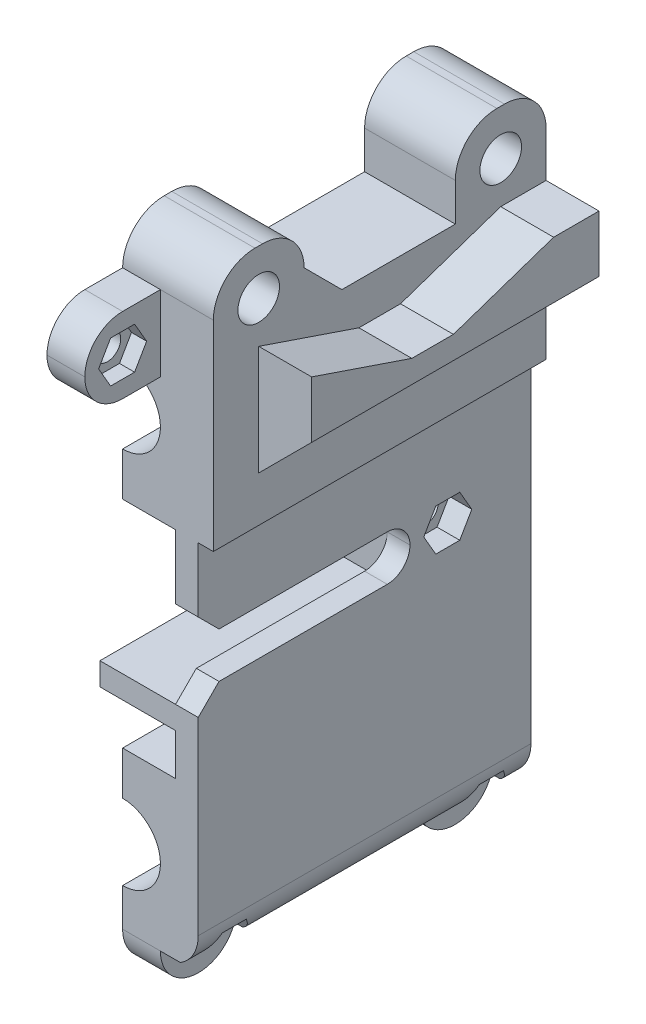
SolidWorks part; units mm, degrees
ref_plane "Front Plane" through (0, 0, 0) normal (0, 0, 1) x (1, 0, 0)
ref_plane "Top Plane" through (0, 0, 0) normal (0, 1, 0) x (1, 0, 0)
ref_plane "Right Plane" through (0, 0, 0) normal (1, 0, 0) x (0, 0, -1)
sketch "Sketch1" plane through (0, 0, 0) normal (1, 0, 0) x (0, 0, -1)
  line L1 (-22, -16) -> (22, -16)
  line L2 (-22, -16) -> (-22, 16)
  line L3 (-22, 16) -> (22, 16)
  line L4 (22, -16) -> (22, 16)
  line L5 (-22, -16) -> (22, 16) construction
  line L6 (-22, 16) -> (22, -16) construction
  point P0 (0, 0)
  dimension "D1" = 44
  dimension "D2" = 32
extrude "Boss-Extrude1" add sketch "Sketch1" along normal blind 12
sketch "Sketch2" plane through (0, 0, 0) normal (1, 0, 0) x (0, 0, -1)
  line L0 (-22, -16) -> (22, -16) construction
  line L1 (12.25, -13) -> (-12.25, -13)
  line L2 (12.25, -13) -> (12.25, 2.5)
  line L3 (12.25, 2.5) -> (-12.25, 2.5)
  line L4 (-12.25, -13) -> (-12.25, 2.5)
  line L5 (12.25, -13) -> (-12.25, 2.5) construction
  line L6 (12.25, 2.5) -> (-12.25, -13) construction
  point P0 (0, -5.25)
  dimension "D1" = 24.5
  dimension "D2" = 15.5
  dimension "D3" = 0
  dimension "D4" = 3
extrude "Cut-Extrude1" cut sketch "Sketch2" along normal blind 7.75 contours L2 L1 L4 L3
fillet "Fillet1" radius 7.75 2 edges at (7.75, 2.5, 0) (7.75, -13, 0)
sketch "Sketch3" plane through (0, 0, -12.25) normal (0, 0, 1) x (1, 0, 0)
  arc A0 (0, -13) -> (7.75, -5.25) centre (0, -5.25) ccw construction
  arc A1 (0, -13) -> (7.75, -5.25) centre (0, -5.25) ccw
  circle A2 centre (0, -5.25) radius 5
  line M3 (0, 2.5) -> (0, -13)
  dimension "D1" = 10
extrude "Cut-Extrude2" cut sketch "Sketch3" against normal through all both and the other way through all contours A2 M3 | A2 M3 region at (2.1221, -5.25, -12.25) region at (-2.1221, -5.25, -12.25)
sketch "Sketch4" plane through (12, 0, 0) normal (1, 0, 0) x (0, 0, -1)
  line L0 (22, 16) -> (-22, 16) construction
  line L2 (-10, 16) -> (10, 16)
  line L3 (-10, 16) -> (-10, 5.5)
  line L4 (-10, 5.5) -> (10, 5.5)
  line L5 (10, 16) -> (10, 5.5)
  circle A0 centre (-16, 10) radius 2.75
  circle A1 centre (16, 10) radius 2.75
  dimension "D1" = 5.5
  dimension "D2" = 5.5
  dimension "D3" = 6
  dimension "D4" = 6
  dimension "D5" = 6
  dimension "D6" = 6
  dimension "D7" = 32
  dimension "D8" = 10
  dimension "D9" = 10.5
extrude "Cut-Extrude3" cut sketch "Sketch4" against normal through all
sketch "Sketch5" plane through (12, 0, 0) normal (1, 0, 0) x (0, 0, -1)
  line L0 (-16, 10) -> (-16, 4.5)
  line L1 (-2.75, -3) -> (2.75, -3)
  line L2 (-2.75, -3) -> (-2.75, 0)
  line L3 (-2.75, 0) -> (2.75, 0)
  line L4 (2.75, -3) -> (2.75, 0)
  line L5 (-2.75, -3) -> (2.75, 0) construction
  line L6 (-2.75, 0) -> (2.75, -3) construction
  line L7 (16, 10) -> (16, 4.5)
  line L8 (-2.75, 0) -> (-16, 4.5)
  line L9 (2.75, 0) -> (16, 4.5)
  line L10 (2.75, -3) -> (16, 4.5)
  line L11 (-2.75, -3) -> (-16, 4.5)
  line L12 (16, 4.5) -> (16, -3)
  line L13 (16, -3) -> (2.75, -3)
  line L14 (-2.75, -3) -> (-16, -3)
  line L15 (-16, -3) -> (-16, 4.5)
  circle A0 centre (16, 10) radius 2.75 construction
  circle A1 centre (16, 10) radius 2.75
  circle A2 centre (-16, 10) radius 2.75 construction
  circle A3 centre (-16, 10) radius 2.75
  point P0 (0, -1.5)
  dimension "D1" = 10
  dimension "D2" = 3
  dimension "D3" = 5.5
  dimension "D4" = 0
  dimension "D5" = 5.5
  dimension "D6" = 5.5
extrude "Boss-Extrude4" add sketch "Sketch5" along normal blind 7 contours L15 L14 L11 | L11 L2 L8 | L1 L4 L3 L2 | L4 L10 L9 | L13 L12 L10 region at (12, 0.5, 7.1667) region at (12, -0.5, 11.5833) region at (12, -1.5, 0) region at (12, 0.5, -7.1667) region at (12, -0.5, -11.5833)
chamfer "Chamfer1" distance 7 angle 45 1 edges at (12, -3, 0)
sketch "Sketch6" plane through (12, 0, 0) normal (1, 0, 0) x (0, 0, -1)
  line L0 (16, -3) -> (-16, -3) construction
  line L1 (16, -3) -> (-16, -3)
  line L2 (16, -10) -> (-16, -10) construction
  line L3 (-13, -3) -> (13, -3)
  line L4 (-13, -3) -> (-13, -10)
  line L5 (-13, -10) -> (13, -10)
  line L6 (13, -3) -> (13, -10)
  line L7 (-16, -10) -> (-16, -3) construction
  line L8 (10, 5.5) -> (-10, 5.5)
  line L9 (-10, 5.5) -> (-10, 16)
  line L10 (-10, 16) -> (-22, 16)
  line L11 (-22, 16) -> (-22, -16)
  line L12 (-22, -16) -> (22, -16)
  line L13 (22, -16) -> (22, 16)
  line L14 (22, 16) -> (10, 16)
  line L15 (10, 16) -> (10, 5.5)
  line L16 (10, 5.5) -> (-10, 5.5)
  line L17 (-10, 5.5) -> (-10, 16)
  line L18 (-10, 16) -> (-22, 16)
  line L19 (-22, 16) -> (-22, -16)
  line L20 (-22, -16) -> (22, -16)
  line L21 (22, -16) -> (22, 16)
  line L22 (22, 16) -> (10, 16)
  line L23 (10, 16) -> (10, 5.5)
  line L24 (16, 4.5) -> (16, -10) construction
  line L25 (-2.75, 0) -> (2.75, 0) construction
  line L26 (-1.5, -3) -> (1.5, -3)
  line L27 (-1.5, -3) -> (-1.5, -10)
  line L28 (-1.5, -10) -> (1.5, -10)
  line L29 (1.5, -3) -> (1.5, -10)
  point P26 (0, 0)
  line M13 (16, -10) -> (-16, -10)
  dimension "D2" = 3
  dimension "D3" = 3
  dimension "D4" = 3
  dimension "D5" = 1.5
  dimension "D1" = 0
extrude "Cut-Extrude5" cut sketch "Sketch6" along normal through all contours L27 L1 L4 L5 | L1 L29 L6 M13 region at (12, -6.5, -7.25) region at (12, -6.5, 7.25)
fillet "Fillet4" radius 5.5 2 edges at (6, 16, -22) (6, 16, 22)
sketch "Sketch7" plane through (0, 0, 0) normal (1, 0, 0) x (0, 0, -1)
  line L0 (-22, -16) -> (22, -16) construction
  line L1 (5, -16) -> (-5, -16)
  line L2 (5, -16) -> (5, -26)
  line L3 (5, -26) -> (-5, -26)
  line L4 (-5, -16) -> (-5, -26)
  circle A0 centre (0, -21) radius 2
  dimension "D4" = 4
  dimension "D1" = 10
  dimension "D2" = 10
  dimension "D3" = 5
  dimension "D5" = 5
extrude "Boss-Extrude5" [suppressed] add sketch "Sketch7" along normal blind 5
sketch "Sketch8" [suppressed] plane through (5, 0, 0) normal (1, 0, 0) x (0, 0, -1)
  line L1 (0, -24.1754) -> (2.75, -22.5877)
  line L2 (2.75, -22.5877) -> (2.75, -19.4123)
  line L3 (2.75, -19.4123) -> (0, -17.8246)
  line L4 (0, -17.8246) -> (-2.75, -19.4123)
  line L5 (-2.75, -19.4123) -> (-2.75, -22.5877)
  line L6 (-2.75, -22.5877) -> (0, -24.1754)
  circle A0 centre (0, -21) radius 2 construction
  circle A1 centre (0, -21) radius 2
  circle A2 centre (0, -21) radius 2.75 construction
  dimension "D1" = 5.5
extrude "Cut-Extrude6" [suppressed] cut sketch "Sketch8" against normal blind 2
fillet "Fillet5" [suppressed] radius 5
sketch "Sketch9" plane through (0, 0, 0) normal (-1, 0, 0) x (0, 0, 1)
  line L1 (-16, 5.3812) -> (-12, 7.6906)
  line L2 (-12, 7.6906) -> (-12, 12.3094)
  line L3 (-12, 12.3094) -> (-16, 14.6188)
  line L4 (-16, 14.6188) -> (-20, 12.3094)
  line L5 (-20, 12.3094) -> (-20, 7.6906)
  line L6 (-20, 7.6906) -> (-16, 5.3812)
  line L7 (16, 5.3812) -> (20, 7.6906)
  line L8 (20, 7.6906) -> (20, 12.3094)
  line L9 (20, 12.3094) -> (16, 14.6188)
  line L10 (16, 14.6188) -> (12, 12.3094)
  line L11 (12, 12.3094) -> (12, 7.6906)
  line L12 (12, 7.6906) -> (16, 5.3812)
  circle A0 centre (16, 10) radius 2.75 construction
  circle A1 centre (-16, 10) radius 2.75 construction
  circle A2 centre (16, 10) radius 2.75
  circle A3 centre (-16, 10) radius 2.75
  circle A4 centre (-16, 10) radius 4 construction
  circle A5 centre (16, 10) radius 4 construction
  point P6 (20, 10)
  dimension "D1" = 8
  dimension "D2" = 8
extrude "Cut-Extrude7" [suppressed] cut sketch "Sketch9" against normal blind 4
ref_plane "Plane1" through (0, -30.25, 0) normal (0, -1, 0) x (-1, 0, 0)
sketch "Sketch10" plane through (0, -16, 0) normal (0, -1, 0) x (1, 0, 0)
  line L0 (12, 22) -> (0, 22) construction
  line L1 (7, 22) -> (10, 22)
  line L2 (7, 22) -> (7, -22)
  line L3 (7, -22) -> (10, -22)
  line L4 (10, 22) -> (10, -22)
  line L5 (12, -22) -> (0, -22) construction
  line L6 (0, 22) -> (0, -22) construction
  dimension "D1" = 3
  dimension "D2" = 7
extrude "Boss-Extrude6" add sketch "Sketch10" along normal blind 28.5
sketch "Sketch11" plane through (0, -44.5, 0) normal (0, -1, 0) x (1, 0, 0)
  line L1 (10, -22) -> (0, -22)
  line L2 (10, -22) -> (10, 22)
  line L3 (10, 22) -> (0, 22)
  line L4 (0, -22) -> (0, 22)
  dimension "D1" = 44
  dimension "D2" = 10
extrude "Boss-Extrude7" add sketch "Sketch11" along normal blind 21.5
sketch "Sketch12" plane through (0, 0, 0) normal (-1, 0, 0) x (0, 0, 1)
  line L0 (22, -44.5) -> (-22, -44.5) construction
  line L1 (-12.25, -63) -> (12.25, -63)
  line L2 (-12.25, -63) -> (-12.25, -47.5)
  line L3 (-12.25, -47.5) -> (12.25, -47.5)
  line L4 (12.25, -63) -> (12.25, -47.5)
  dimension "D1" = 24.5
  dimension "D2" = 15.5
  dimension "D3" = 3
  dimension "D4" = 12.25
extrude "Cut-Extrude8" cut sketch "Sketch12" against normal blind 7.75
fillet "Fillet6" radius 7.75 2 edges at (7.75, -63, 0) (7.75, -47.5, 0)
sketch "Sketch13" plane through (0, 0, 22) normal (0, 0, 1) x (1, 0, 0)
  arc A0 (7.75, -55.25) -> (0, -47.5) centre (0, -55.25) ccw construction
  arc A1 (7.75, -55.25) -> (0, -47.5) centre (0, -55.25) ccw
  circle A2 centre (0, -55.25) radius 5
  line M9 (0, -44.5) -> (0, -66)
  dimension "D1" = 10
extrude "Cut-Extrude9" cut sketch "Sketch13" against normal through all contours A2 M9 region at (2.1221, -55.25, 22)
sketch "Sketch14" plane through (7, 0, 0) normal (-1, 0, 0) x (0, 0, 1)
  line L1 (-22, -16) -> (-6, -16)
  line L2 (-22, -16) -> (-22, -36)
  line L3 (-22, -36) -> (-6, -36)
  line L4 (-6, -16) -> (-6, -36)
  dimension "D1" = 20
  dimension "D2" = 16
extrude "Boss-Extrude8" add sketch "Sketch14" along normal blind 13.5
sketch "Sketch15" plane through (-6.5, 0, 0) normal (-1, 0, 0) x (0, 0, 1)
  line L0 (-6.6, -30.25) -> (6.6, -30.25) construction
  line L1 (-22, -16) -> (-22, -36) construction
  line L2 (-22, -29) -> (-11, -29)
  line L3 (-22, -29) -> (-22, -31.5)
  line L4 (-22, -31.5) -> (-11, -31.5)
  line L5 (-11, -29) -> (-11, -31.5)
  circle A0 centre (-11, -30.25) radius 3
  line M6 (-22, -16) -> (-22, -36)
  dimension "D2" = 6
  dimension "D1" = 0
  dimension "D3" = 2.5
  dimension "D4" = 1.25
  dimension "D5" = 11
extrude "Cut-Extrude10" cut sketch "Sketch15" against normal blind 10 contours A0 L2 L4 M6 | L2 A0 L4 L5 | L4 A0 L2 L5 region at (-6.5, -30.25, -17.955) region at (-6.5, -30.25, -10.4952) region at (-6.5, -30.25, -12.4565)
fillet "Fillet7" radius 2 2 edges at (-1.5, -29, -13.7272) (-1.5, -31.5, -13.7272)
sketch "Sketch16" plane through (3.5, 0, 0) normal (-1, 0, 0) x (0, 0, 1)
  arc A0 (-13.2798, -32.2) -> (-13.2798, -28.3) centre (-11, -30.25) ccw construction
  arc A1 (-13.2798, -32.2) -> (-13.2798, -28.3) centre (-11, -30.25) ccw
  circle A2 centre (-11, -30.25) radius 1.75
  point P4 (0, 0)
  dimension "D1" = 3.5
extrude "Cut-Extrude11" cut sketch "Sketch16" against normal through all contours A2 region at (3.5, -30.25, -11)
sketch "Sketch17" plane through (10, 0, 0) normal (1, 0, 0) x (0, 0, -1)
  line L1 (14.1754, -30.25) -> (12.5877, -27.5)
  line L2 (12.5877, -27.5) -> (9.4123, -27.5)
  line L3 (9.4123, -27.5) -> (7.8246, -30.25)
  line L4 (7.8246, -30.25) -> (9.4123, -33)
  line L5 (9.4123, -33) -> (12.5877, -33)
  line L6 (12.5877, -33) -> (14.1754, -30.25)
  circle A0 centre (11, -30.25) radius 1.75 construction
  circle A1 centre (11, -30.25) radius 1.75
  circle A2 centre (11, -30.25) radius 2.75 construction
  dimension "D1" = 5.5
extrude "Cut-Extrude12" cut sketch "Sketch17" against normal blind 3
sketch "Sketch18" plane through (7, 0, 0) normal (-1, 0, 0) x (0, 0, 1)
  line L0 (22, -44.5) -> (22, -16) construction
  line L1 (-22, -36) -> (22, -36)
  line L2 (-22, -36) -> (-22, -39)
  line L3 (-22, -39) -> (22, -39)
  line L4 (22, -36) -> (22, -39)
  dimension "D1" = 3
extrude "Boss-Extrude9" add sketch "Sketch18" along normal blind 10
sketch "Sketch20" plane through (-6.5, 0, 0) normal (-1, 0, 0) x (0, 0, 1)
  line L1 (-22, -16) -> (-11, -16)
  line L2 (-22, -16) -> (-22, -25)
  line L3 (-22, -25) -> (-11, -25)
  line L4 (-11, -16) -> (-11, -25)
  dimension "D1" = 9
  dimension "D2" = 11
extrude "Cut-Extrude13" cut sketch "Sketch20" against normal up to surface (13.5 mm away) up to face at (7, -26, 8)
sketch "Sketch21" plane through (0, 0, -11) normal (0, 0, -1) x (-1, 0, 0)
  line L0 (0, -16) -> (6.5, -16) construction
  circle A0 centre (0, -20.5) radius 1.75
  dimension "D2" = 3.5
  dimension "D1" = 4.5
extrude "Cut-Extrude14" cut sketch "Sketch21" against normal up to surface (5 mm away) up to face at (-0.3333, -26, -6)
sketch "Sketch22" plane through (0, 0, -11) normal (0, 0, -1) x (-1, 0, 0)
  line L1 (3.1754, -20.5) -> (1.5877, -17.75)
  line L2 (1.5877, -17.75) -> (-1.5877, -17.75)
  line L3 (-1.5877, -17.75) -> (-3.1754, -20.5)
  line L4 (-3.1754, -20.5) -> (-1.5877, -23.25)
  line L5 (-1.5877, -23.25) -> (1.5877, -23.25)
  line L6 (1.5877, -23.25) -> (3.1754, -20.5)
  circle A0 centre (0, -20.5) radius 1.75 construction
  circle A1 centre (0, -20.5) radius 1.75
  circle A2 centre (0, -20.5) radius 2.75 construction
  dimension "D1" = 5.5
extrude "Cut-Extrude15" cut sketch "Sketch22" against normal blind 2
sketch "Sketch23" plane through (7, 0, 0) normal (-1, 0, 0) x (0, 0, 1)
  line L0 (-6.6, -30.25) -> (6.6, -30.25) construction
  line L1 (-6, -27.25) -> (22, -27.25)
  line L2 (-6, -27.25) -> (-6, -33.25)
  line L3 (-6, -33.25) -> (22, -33.25)
  line L4 (22, -27.25) -> (22, -33.25)
  line L5 (-6, -27.25) -> (22, -33.25) construction
  line L6 (-6, -33.25) -> (22, -27.25) construction
  line L7 (-6, -36) -> (-6, -16) construction
  line L8 (22, -36) -> (22, -16) construction
  point P0 (8, -30.25)
  dimension "D1" = 0
  dimension "D2" = 0
  dimension "D3" = 0
  dimension "D4" = 6
extrude "Cut-Extrude16" cut sketch "Sketch23" against normal through all
fillet "Fillet8" radius 3 2 edges at (8.5, -27.25, -6) (8.5, -33.25, -6)
chamfer "Chamfer2" distance 2.75 angle 45 2 edges at (8.5, -27.25, 22) (8.5, -33.25, 22)
chamfer "Chamfer3" distance 3 angle 45 1 edges at (0.25, -25, -11)
fillet "Fillet9" radius 3 1 edges at (-6.5, -16, -8.5)
ref_plane "Plane2" through (0, 5.5, -10) normal (0, 1, 0) x (1, 0, 0)
sketch "Sketch25" plane through (0, 0, 0) normal (-1, 0, 0) x (0, 0, 1)
  line L1 (22, 10.5) -> (32, 10.5)
  line L2 (22, 10.5) -> (22, 0.5)
  line L3 (22, 0.5) -> (32, 0.5)
  line L4 (32, 10.5) -> (32, 0.5)
  dimension "D1" = 10
  dimension "D2" = 10
extrude "Boss-Extrude12" add sketch "Sketch25" against normal blind 5
fillet "Fillet11" radius 5 2 edges at (2.5, 0.5, 32) (2.5, 10.5, 32)
sketch "Sketch26" plane through (0, 0, 0) normal (-1, 0, 0) x (0, 0, 1)
  line L0 (-12.25, -63) -> (12.25, -63) construction
  line L1 (-22, -60.25) -> (-12, -60.25)
  line L2 (-22, -60.25) -> (-22, -70.25)
  line L3 (-22, -70.25) -> (-12, -70.25)
  line L4 (-12, -60.25) -> (-12, -70.25)
  line L5 (22, -60.25) -> (12, -60.25)
  line L6 (22, -60.25) -> (22, -70.25)
  line L7 (22, -70.25) -> (12, -70.25)
  line L8 (12, -60.25) -> (12, -70.25)
  line L9 (12.2369, -63) -> (12, -63)
  line L10 (12.2369, -63) -> (12.2369, -60.25)
  line L11 (12.2369, -60.25) -> (12, -60.25)
  line L12 (12, -63) -> (12, -60.25)
  line L14 (-12.25, -63) -> (-12, -63)
  line L15 (-12.25, -63) -> (-12.25, -60.25)
  line L16 (-12.25, -60.25) -> (-12, -60.25)
  line L17 (-12, -63) -> (-12, -60.25)
  line M14 (-22, -66) -> (22, -66)
  dimension "D1" = 10
  dimension "D2" = 10
  dimension "D3" = 10
  dimension "D4" = 10
extrude "Boss-Extrude13" add sketch "Sketch26" against normal blind 5 contours L4 L2 L3 M14 | L8 L7 L6 M14 region at (0, -68.125, 17) region at (0, -68.125, -17)
sketch "Sketch27" plane through (0, 0, 0) normal (-1, 0, 0) x (0, 0, 1)
  line L0 (-22, -70.25) -> (-12, -70.25) construction
  line L1 (-22, -70.25) -> (-22, -60.25) construction
  line L2 (22, -70.25) -> (22, -60.25) construction
  line L3 (22, -70.25) -> (12, -70.25) construction
  circle A0 centre (-17, -65.25) radius 1.75
  circle A1 centre (17, -65.25) radius 1.75
  point P8 (-22, -65.25)
  dimension "D5" = 3.5
  dimension "D6" = 3.5
  dimension "D1" = 5
  dimension "D2" = 5
  dimension "D3" = 5
  dimension "D4" = 5
extrude "Cut-Extrude17" cut sketch "Sketch27" against normal through all both and the other way through all
sketch "Sketch28" plane through (5, 0, 0) normal (1, 0, 0) x (0, 0, -1)
  line L1 (-13.8246, -65.25) -> (-15.4123, -62.5)
  line L2 (-15.4123, -62.5) -> (-18.5877, -62.5)
  line L3 (-18.5877, -62.5) -> (-20.1754, -65.25)
  line L4 (-20.1754, -65.25) -> (-18.5877, -68)
  line L5 (-18.5877, -68) -> (-15.4123, -68)
  line L6 (-15.4123, -68) -> (-13.8246, -65.25)
  line L7 (20.1754, -65.25) -> (18.5877, -62.5)
  line L8 (18.5877, -62.5) -> (15.4123, -62.5)
  line L9 (15.4123, -62.5) -> (13.8246, -65.25)
  line L10 (13.8246, -65.25) -> (15.4123, -68)
  line L11 (15.4123, -68) -> (18.5877, -68)
  line L12 (18.5877, -68) -> (20.1754, -65.25)
  circle A0 centre (17, -65.25) radius 1.75 construction
  circle A1 centre (-17, -65.25) radius 1.75 construction
  circle A2 centre (17, -65.25) radius 1.75
  circle A3 centre (-17, -65.25) radius 1.75
  circle A4 centre (-17, -65.25) radius 2.75 construction
  circle A5 centre (17, -65.25) radius 2.75 construction
  dimension "D1" = 5.5
  dimension "D2" = 5.5
extrude "Cut-Extrude19" cut sketch "Sketch28" against normal blind 2 and the other way through all
fillet "Fillet14" radius 5 1 edges at (10, -66, 20.8712)
fillet "Fillet15" radius 5 4 edges at (2.5, -70.25, 12) (2.5, -70.25, -12) (2.5, -70.25, -22) (2.5, -70.25, 22)
sketch "Sketch29" plane through (0, 0, 0) normal (-1, 0, 0) x (0, 0, 1)
  arc A0 (32, 5.5) -> (27, 10.5) centre (27, 5.5) ccw construction
  arc A1 (32, 5.5) -> (27, 10.5) centre (27, 5.5) ccw
  circle A2 centre (27, 5.5) radius 1.75
  dimension "D1" = 3.5
extrude "Cut-Extrude20" cut sketch "Sketch29" against normal through all both and the other way through all contours A2 region at (0, 5.5, 27)
sketch "Sketch30" plane through (5, 0, 0) normal (1, 0, 0) x (0, 0, -1)
  line L1 (-23.8246, 5.5) -> (-25.4123, 8.25)
  line L2 (-25.4123, 8.25) -> (-28.5877, 8.25)
  line L3 (-28.5877, 8.25) -> (-30.1754, 5.5)
  line L4 (-30.1754, 5.5) -> (-28.5877, 2.75)
  line L5 (-28.5877, 2.75) -> (-25.4123, 2.75)
  line L6 (-25.4123, 2.75) -> (-23.8246, 5.5)
  circle A0 centre (-27, 5.5) radius 1.75 construction
  circle A1 centre (-27, 5.5) radius 1.75
  circle A2 centre (-27, 5.5) radius 2.75 construction
  dimension "D1" = 5.5
extrude "Cut-Extrude21" cut sketch "Sketch30" against normal blind 2
fillet "Fillet17" radius 5.5 2 edges at (6, 16, -10) (6, 16, 10)
chamfer "Chamfer4" distance 5 angle 45 1 edges at (6, 5.5, 10)
sketch "Sketch32" plane through (0, 0, -16) normal (0, 0, -1) x (-1, 0, 0)
  line L4 (-12, -10) -> (-12, 4.5)
  line L5 (-12, 4.5) -> (-19, 4.5)
  line L6 (-19, 4.5) -> (-19, -3)
  line L7 (-19, -3) -> (-12, -10)
  line L8 (-12, -10) -> (-12, 4.5)
  line L9 (-12, 4.5) -> (-19, 4.5)
  line L10 (-19, 4.5) -> (-19, -3)
  line L11 (-19, -3) -> (-12, -10)
  dimension "D1" = 0
extrude "Boss-Extrude14" add sketch "Sketch32" along normal up to surface (6 mm away) up to face at (2.6074, -30.6323, -22)
sketch "Sketch33" plane through (0, 0, 0) normal (-1, 0, 0) x (0, 0, 1)
  line L1 (11.3812, 10) -> (13.6906, 6)
  line L2 (13.6906, 6) -> (18.3094, 6)
  line L3 (18.3094, 6) -> (20.6188, 10)
  line L4 (20.6188, 10) -> (18.3094, 14)
  line L5 (18.3094, 14) -> (13.6906, 14)
  line L6 (13.6906, 14) -> (11.3812, 10)
  line L7 (-11.3812, 10) -> (-13.6906, 14)
  line L8 (-13.6906, 14) -> (-18.3094, 14)
  line L9 (-18.3094, 14) -> (-20.6188, 10)
  line L10 (-20.6188, 10) -> (-18.3094, 6)
  line L11 (-18.3094, 6) -> (-13.6906, 6)
  line L12 (-13.6906, 6) -> (-11.3812, 10)
  circle A0 centre (-16, 10) radius 2.75 construction
  circle A1 centre (-16, 10) radius 2.75
  circle A2 centre (16, 10) radius 2.75 construction
  circle A3 centre (16, 10) radius 2.75
  circle A4 centre (16, 10) radius 4 construction
  circle A5 centre (-16, 10) radius 4 construction
  dimension "D1" = 8
  dimension "D2" = 8
extrude "Cut-Extrude22" cut sketch "Sketch33" against normal blind 4.5
chamfer "Chamfer11" distance 7 angle 45 2 edges at (15.5, -3, 13) (15.5, -3, -1.5)
sketch "Sketch34" plane through (5, 0, 0) normal (1, 0, 0) x (0, 0, -1)
  line L0 (13.8246, -65.25) -> (15.4123, -68) construction
  line L1 (-19.7424, -66) -> (-20.1754, -65.25) construction
  line L2 (13.8246, -65.25) -> (15.4123, -68)
  line L3 (-19.7424, -66) -> (-20.1754, -65.25)
  line L5 (-24.8945, -70.6786) -> (23.1824, -70.6786)
  line L6 (-24.8945, -70.6786) -> (-24.8945, -65.25)
  line L7 (-24.8945, -65.25) -> (23.1824, -65.25)
  line L8 (23.1824, -70.6786) -> (23.1824, -65.25)
extrude "Cut-Extrude24" cut sketch "Sketch34" along normal through all contours L8 L0 L1 L2 L3 L5 L6 L7 | L5 L8 L7 L6 L3 L2 L1 L0 region at (5, -67.9643, 0.856)
